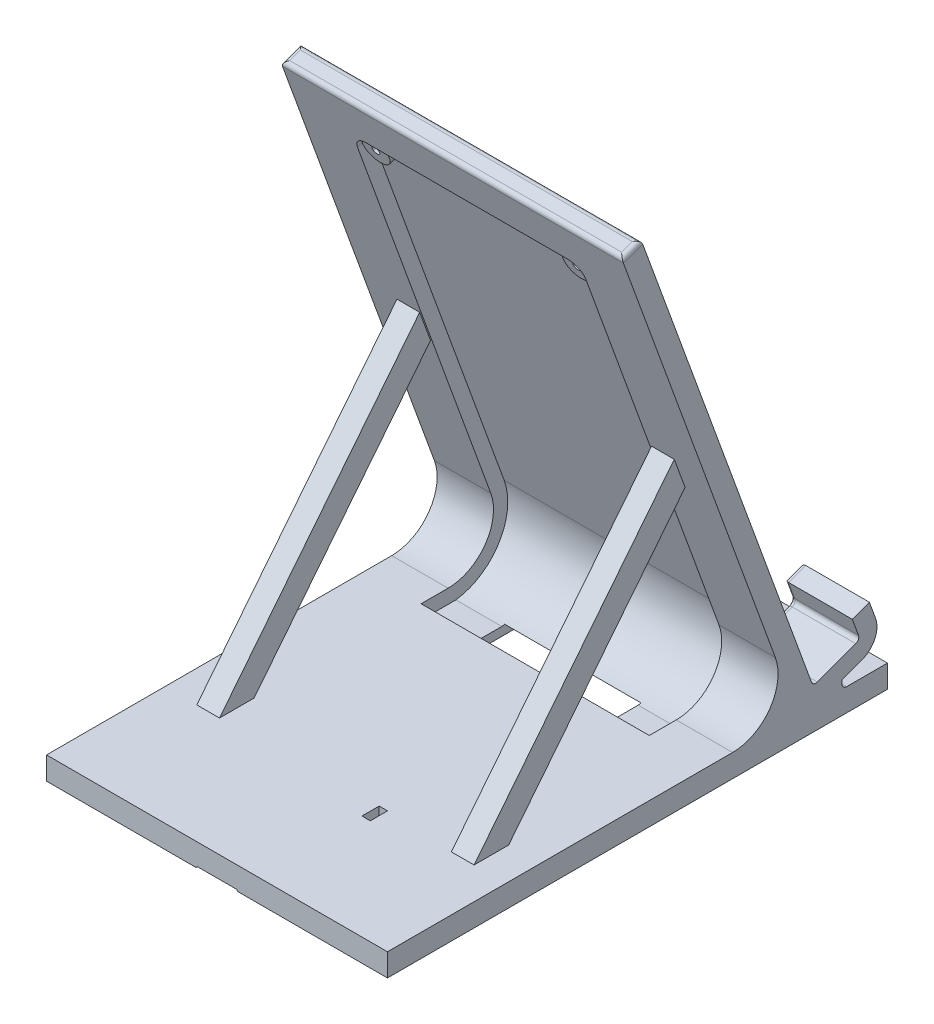
SolidWorks part; units mm, degrees
material "PLA"
ref_plane "前视基准面" through (0, 0, 0) normal (0, 0, 1) x (1, 0, 0)
ref_plane "上视基准面" through (0, 0, 0) normal (0, 1, 0) x (1, 0, 0)
ref_plane "右视基准面" through (0, 0, 0) normal (1, 0, 0) x (0, 0, -1)
other "Configuration Table"
sketch "草图1" plane through (0, 0, 0) normal (0, 1, 0) x (1, 0, 0)
  line L1 (-37.5, -55) -> (37.5, -55)
  line L2 (-37.5, -55) -> (-37.5, 55)
  line L3 (-37.5, 55) -> (37.5, 55)
  line L4 (37.5, -55) -> (37.5, 55)
  line L5 (-37.5, -55) -> (37.5, 55) construction
  line L6 (-37.5, 55) -> (37.5, -55) construction
  point P0 (0, 0)
  dimension "D1" = 75
  dimension "D2" = 110
extrude "底座凸台-拉伸1" add sketch "草图1" along normal blind 5
sketch "草图2" plane through (-37.5, 0, 0) normal (-1, 0, 0) x (0, 0, 1)
  line L0 (-35.2112, 5) -> (3.4371, 111.1853)
  line L1 (55, 5) -> (-55, 5) construction
  line L2 (3.4371, 111.1853) -> (-0.7915, 112.7244)
  line L3 (-0.7915, 112.7244) -> (-40, 5)
  line L4 (-55, 5) -> (-55, 0) construction
  line L5 (-40, 5) -> (-35.2112, 5)
  dimension "D1" = 4.5
  dimension "D2" = 70
  dimension "D3" = 15
  dimension "D4" = 113
extrude "支架面板凸台-拉伸2" add sketch "草图2" against normal up to surface (75 mm away) up to face at (37.5, 2.5, 0)
sketch "草图4" plane through (37.5, 0, 0) normal (1, 0, 0) x (0, 0, -1)
  line L0 (45, 6.8199) -> (49.3969, 8.4202)
  line L1 (52.3853, 14.8288) -> (51.0172, 18.5875)
  line L2 (51.0172, 18.5875) -> (47.2584, 17.2195)
  line L3 (47.2584, 17.2195) -> (48.6265, 13.4607)
  line L4 (38.6319, 8.7588) -> (48.0288, 12.179)
  line L5 (40, 5) -> (0.7915, 112.7244) construction
  line L6 (38.6319, 8.7588) -> (40, 5)
  line L9 (45, 5) -> (40, 5)
  line L10 (45, 6.8199) -> (45, 5)
  arc A0 (49.3969, 8.4202) -> (52.3853, 14.8288) centre (47.6868, 13.1187) ccw
  arc A1 (48.0288, 12.179) -> (48.6265, 13.4607) centre (47.6868, 13.1187) ccw
  dimension "D6" = 1
  dimension "D1" = 90
  dimension "D2" = 90
  dimension "D3" = 10
  dimension "D4" = 4
  dimension "D5" = 4
  dimension "D7" = 5
  dimension "D8" = 4
extrude "支点凸台-拉伸4" add sketch "草图4" against normal blind 15
mirror "镜向1" about plane through (0, 0, 0) normal (1, 0, 0) of "支点凸台-拉伸4"
fillet "圆角1" radius 10 1 edges at (0, 5, -35.2112)
sketch "草图5" plane through (-37.5, 0, 0) normal (-1, 0, 0) x (0, 0, 1)
  line L0 (-17.4763, 53.7262) -> (-15.091, 60.2798)
  line L1 (-30.3266, 18.4202) -> (3.4371, 111.1853) construction
  line L2 (-15.091, 60.2798) -> (28.9432, 5)
  line L3 (-20.9297, 5) -> (55, 5) construction
  line L4 (28.9432, 5) -> (21.3375, 5)
  line L5 (21.3375, 5) -> (-17.4763, 53.7262)
extrude "凸台-拉伸1" add sketch "草图5" along normal blind 5 from offset 12 offset against normal yes
mirror "镜向2" about plane through (0, 0, 0) normal (1, 0, 0) of "凸台-拉伸1"
sketch "草图7" plane through (0, 0, 0) normal (1, 0, 0) x (0, 0, -1)
  line L0 (2.8962, 102.8486) -> (-0.0169, 101.7883)
  line L2 (-3.4371, 111.1853) -> (30.3088, 18.4692) construction
  line L4 (-0.524, 112.2455) -> (33.2792, 19.3718) construction
  line L6 (15, 5) -> (20.7807, 5)
  line L7 (15, 1.9) -> (22.6528, 1.9)
  line L19 (-3.4371, 111.1853) -> (30.3266, 18.4202) construction
  line L20 (0.7915, 112.7244) -> (-3.4371, 111.1853) construction
  line L21 (30.3088, 18.4692) -> (20.9297, 15)
  line L22 (20.9297, 15) -> (20.7807, 5)
  line L23 (-55, 5) -> (-55, 0) construction
  line L33 (15, 5) -> (15, 1.9)
  line L45 (-0.0169, 101.7883) -> (30.3088, 18.4692)
  line L46 (2.8962, 102.8486) -> (33.2792, 19.3718)
  arc A6 (20.9297, 5) -> (30.3266, 18.4202) centre (20.9297, 15) ccw construction
  arc A19 (21.1077, 1.9173) -> (33.2792, 19.3718) centre (19.6222, 15.9242) ccw construction
  arc A20 (20.7807, 5) -> (30.3088, 18.4692) centre (19.6222, 15.9242) ccw construction
  arc A21 (33.2792, 19.3718) -> (22.6528, 1.9) centre (20.9693, 14.8914) cw
  dimension "D3" = 10
  dimension "D4" = 13.1
  dimension "D1" = 3.1
  dimension "D2" = 3.1
  dimension "D5" = 70
extrude "线圈槽位切除-拉伸2" cut sketch "草图7" against normal mid plane 50.2
sketch "草图8" plane through (0, 0, 0) normal (0, -1, 0) x (1, 0, 0)
  line L0 (0, 0) -> (0, -42.2617) construction
  line L1 (-5.9, 53.5) -> (5.9, 53.5)
  line L2 (-15, 39.7) -> (-15, -46.5)
  line L3 (-15, -46.5) -> (15, -46.5)
  line L4 (15, 39.7) -> (15, -46.5)
  line L5 (-5.8, 53.5) -> (-5.8, 39.7) construction
  line L6 (5.9, 53.5) -> (5.9, 39.7)
  line L7 (5.9, 39.7) -> (15, 39.7)
  line L8 (-5.9, 53.5) -> (-5.9, 39.7)
  line L9 (-5.9, 39.7) -> (-15, 39.7)
  line L10 (-37.5, 55) -> (37.5, 55) construction
  line L11 (-5.8, 39.7) -> (5.8, 39.7) construction
  line L12 (5.8, 39.7) -> (5.8, 53.5) construction
  dimension "D1" = 30
  dimension "D2" = 100
  dimension "D3" = 0.1
  dimension "D5" = 1.5
  dimension "D6" = 0.1
extrude "零件槽位切除-拉伸3" cut sketch "草图8" against normal blind 2
fillet "手机支点圆角2" radius 1 28 edges at (22.5, 15.3401, -47.9425) (22.5, 12.696, -48.5931) (22.5, 16.7082, -51.7012) (22.5, 11.0056, -52.2184) (22.5, 5.9099, -45) (22.5, 17.9035, -49.1378) (22.5, 10.4689, -43.3304) (22.5, 7.62, -47.1985) (-30, 8.7588, -38.6319) (-30, 5, -45) (30, 5, -45) (30, 8.7588, -38.6319) (0, 111.1853, 3.4371) (0, 112.7244, -0.7915) (37.5, 111.9548, 1.3228) (-37.5, 111.9548, 1.3228) (-22.5, 6.8794, -39.316) (-22.5, 10.4689, -43.3304) (-22.5, 12.696, -48.5931) (-22.5, 15.3401, -47.9425) (-22.5, 17.9035, -49.1378) (-22.5, 16.7082, -51.7012) (-22.5, 11.0056, -52.2184) (-22.5, 7.62, -47.1985) (-22.5, 5.9099, -45) (-22.5, 5, -42.5) (22.5, 6.8794, -39.316) (22.5, 5, -42.5)
sketch "草图9" plane through (0, 0, 55) normal (0, 0, 1) x (1, 0, 0)
  line L1 (-4.6, 0.3) -> (4.6, 0.3)
  line L2 (-4.6, 0.3) -> (-4.6, -0.8)
  line L3 (-4.6, -0.8) -> (4.6, -0.8)
  line L4 (4.6, 0.3) -> (4.6, -0.8)
  line L6 (4.5, -1.9) -> (4.5, -0.8) construction
  line L7 (-4.5, -1.9) -> (-4.5, -0.8) construction
  line L11 (-3.5, 0.2) -> (3.5, 0.2) construction
  dimension "D1" = 0.1
  dimension "D2" = 0.1
  dimension "D3" = 1
  dimension "D4" = 0.1
sketch "草图10" plane through (0, 0, 0) normal (0, 1, 0) x (1, 0, 0)
  circle A0 centre (-18, -34) radius 1
  circle A1 centre (18, -34) radius 1
  circle A2 centre (18, 34) radius 1
  circle A3 centre (-18, 34) radius 1
  dimension "D1" = 2
  dimension "D2" = 2
  dimension "D3" = 2
  dimension "D4" = 2
extrude "拉伸-薄壁1" add sketch "草图10" against normal up to surface (2 mm away) thin thin type one direction wall 2
sketch "草图11" plane through (0, 0, 0) normal (0, 1, 0) x (1, 0, 0)
  line L0 (-18, -28) -> (-18, 28)
  line L1 (18, -28) -> (18, 28)
  circle A0 centre (-18, -34) radius 6 construction
  circle A1 centre (-18, 34) radius 6 construction
  circle A2 centre (18, -34) radius 6 construction
  circle A3 centre (18, 34) radius 6 construction
extrude "拉伸-薄壁2" add sketch "草图11" against normal up to surface (2.4 mm away) thin thin type mid plane wall 1
extrude "切除-拉伸1" cut sketch "草图9" against normal up to surface (1.5 mm away)
sketch "草图12" plane through (0, 2, 0) normal (0, -1, 0) x (1, 0, 0)
  line L0 (7.9, 34.3906) -> (11.6, 34.3906)
  line L1 (8, 34.2906) -> (11.5, 34.2906) construction
  line L2 (8, 34.2906) -> (8, 25.7906) construction
  line L3 (8, 25.7906) -> (11.5, 25.7906) construction
  line L4 (11.5, 34.2906) -> (11.5, 25.7906) construction
  line L5 (11.6, 34.3906) -> (11.6, 25.6906)
  line L6 (7.9, 25.6906) -> (11.6, 25.6906)
  line L7 (7.9, 34.3906) -> (7.9, 25.6906)
  dimension "D1" = 0.1
extrude "开关拉伸-薄壁3" add sketch "草图12" along normal blind 3 thin thin type one direction wall 1.5
fillet "充电口圆角2" radius 0.5 2 edges at (-4.6, 0.3, 54.25) (4.6, 0.3, 54.25)
sketch "草图13" plane through (0, 2, 0) normal (0, -1, 0) x (1, 0, 0)
  line L0 (-8, 20.3812) -> (-8, 17.3812) construction
  line L1 (-8, 17.3812) -> (-10.5, 17.3812) construction
  line L2 (-10.5, 17.3812) -> (-10.5, -7.6188) construction
  line L3 (-10.5, -7.6188) -> (10.5, -7.6188) construction
  line L4 (10.5, -7.6188) -> (10.5, 17.3812) construction
  line L5 (10.5, 17.3812) -> (8, 17.3812) construction
  line L6 (8, 17.3812) -> (8, 20.3812) construction
  line L7 (8, 17.3812) -> (8, 20.3812) construction
  line L8 (8, 20.3812) -> (-8, 20.3812) construction
  line L9 (8, 20.3812) -> (-8, 20.3812) construction
  line L10 (10.5, 0.3812) -> (10.5, 17.3812) construction
  line L11 (-3.5, -7.6188) -> (3.5, -7.6188) construction
  line L12 (-8.1, 20.4812) -> (-8.1, 17.4812)
  line L13 (-8.1, 17.4812) -> (-10.6, 17.4812)
  line L14 (-10.6, 17.4812) -> (-10.6, -7.7188)
  line L15 (-10.6, -7.7188) -> (10.6, -7.7188)
  line L16 (10.6, -7.7188) -> (10.6, 17.4812)
  line L17 (10.6, 17.4812) -> (8.1, 17.4812)
  line L18 (8.1, 17.4812) -> (8.1, 20.4812)
  line L19 (8.1, 20.4812) -> (-8.1, 20.4812)
  dimension "D1" = 0.1
extrude "电路板固定拉伸-薄壁4" add sketch "草图13" along normal up to surface (2 mm away) thin up to face at (0.5, 0, 16.2417) thin type one direction wall 1.5
sketch "草图14" plane through (0, 2, 0) normal (0, -1, 0) x (1, 0, 0)
  line L0 (5.9, 39.7) -> (5.9, 39.6)
  line L1 (5.9, 39.6) -> (-5.9, 39.6)
  line L2 (-5.9, 39.6) -> (-5.9, 39.7)
  line L3 (-5.8, 39.7) -> (5.8, 39.7) construction
  line L4 (15, 39.7) -> (5.9, 39.7) construction
  line L7 (-5.9, 53.5) -> (-5.9, 39.7) construction
  line L8 (-5.9, 39.7) -> (-15, 39.7) construction
  line L17 (-5.9, 39.7) -> (-10.9, 39.7)
  line L21 (10.9, 39.7) -> (5.9, 39.7)
  dimension "D2" = 0.1
  dimension "D1" = 5
  dimension "D3" = 5
extrude "充电口拉伸-薄壁5" add sketch "草图14" along normal up to surface (2 mm away) thin up to face at (0.5, 0, 16.2417) thin type one direction reverse wall 2
sketch "草图15" plane through (0, 0, 0) normal (0, -1, 0) x (1, 0, 0)
  circle A0 centre (-18, 34) radius 1 construction
  circle A1 centre (-18, 34) radius 1
  circle A2 centre (18, 34) radius 1 construction
  circle A3 centre (18, 34) radius 1
  circle A4 centre (18, -34) radius 1 construction
  circle A5 centre (-18, -34) radius 1 construction
  circle A6 centre (18, -34) radius 1
  circle A7 centre (-18, -34) radius 1
extrude "螺丝孔切除-拉伸2" cut sketch "草图15" against normal blind 2
sketch "草图18" plane through (0, 5, 0) normal (0, 1, 0) x (1, 0, 0)
  line L0 (0, 55) -> (0, 40) construction
  line L1 (37.5, 55) -> (-37.5, 55) construction
  line L2 (21.5, 40) -> (-21.5, 40) construction
  line L3 (12.8007, 50) -> (-12.8007, 50) construction
  text T0 "Alice Feng"
  dimension "D1" = 5
extrude "切除-拉伸2" cut sketch "草图18" against normal blind 0.25
sketch "草图19" plane through (0, 12.9618, -35.6123) normal (0, -0.342, 0.9397) x (1, 0, 0)
  line L0 (0, 95.6555) -> (0, 75.4237) construction
  line L1 (-25.1, 95.6555) -> (25.1, 95.6555) construction
  line L2 (-25.1, 95.6555) -> (-25.1, 6.937) construction
  line L7 (25.1, 95.6555) -> (25.1, 92.6555)
  line L8 (22.1, 95.6555) -> (25.1, 95.6555)
  line L9 (-25.1, 92.6555) -> (-25.1, 95.6555)
  line L11 (-25.1, 95.6555) -> (-22.1, 95.6555)
  arc A2 (-25.1, 92.6555) -> (-22.1, 95.6555) centre (-22.1, 92.6555) ccw
  circle A3 centre (-22.1, 92.6555) radius 0.825
  circle A4 centre (22.1, 92.6555) radius 0.825
  arc A5 (25.1, 92.6555) -> (22.1, 95.6555) centre (22.1, 92.6555) cw
  dimension "D3" = 1.65
  dimension "D1" = 3
  dimension "D2" = 3
extrude "凸台-拉伸2" add sketch "草图19" along normal blind 2
sketch "草图20" plane through (0, 12.2778, -33.7329) normal (0, -0.342, 0.9397) x (1, 0, 0)
  line L0 (-25.1, 92.6555) -> (-25.1, 95.6555)
  line L1 (-25.1, 95.6555) -> (-22.1, 95.6555)
  line L2 (0, 95.6555) -> (0, 71.8622) construction
  line L3 (-25.1, 95.6555) -> (25.1, 95.6555) construction
  line L5 (25.1, 95.6555) -> (22.1, 95.6555)
  line L12 (25.1, 92.6555) -> (25.1, 95.6555)
  arc A0 (-25.1, 92.6555) -> (-22.1, 95.6555) centre (-22.1, 92.6555) ccw construction
  arc A6 (-22.1, 95.6555) -> (-25.1, 92.6555) centre (-22.1, 92.6555) ccw
  arc A7 (22.1, 95.6555) -> (25.1, 92.6555) centre (22.1, 92.6555) cw
extrude "凸台-拉伸3" add sketch "草图20" along normal blind 1.1
sketch "草图22" plane through (0, 0, 0) normal (0, 0, 1) x (1, 0, 0)
  line L0 (0, 0) -> (0, 9.0871) construction
  line L1 (-25.1, 3.3) -> (-5.4, 3.3)
  line L2 (-25.1, 3.3) -> (-25.1, 1.9)
  line L3 (-25.1, 1.9) -> (-5.4, 1.9)
  line L4 (-5.4, 3.3) -> (-5.4, 1.9)
  line L5 (-5.5, 3.2) -> (-25, 3.2) construction
  line L6 (-5.5, 2) -> (-5.5, 19.4463) construction
  line L7 (-15, 2) -> (15, 2) construction
  line L8 (-25, 19.4463) -> (-25, 2) construction
  line L9 (5.4, 3.3) -> (5.4, 1.9)
  line L10 (25.1, 1.9) -> (5.4, 1.9)
  line L11 (25.1, 3.3) -> (25.1, 1.9)
  line L12 (25.1, 3.3) -> (5.4, 3.3)
  dimension "D1" = 0.1
  dimension "D2" = 0.1
  dimension "D3" = 0.1
  dimension "D4" = 0.1
extrude "切除-拉伸3" cut sketch "草图22" along normal blind 2.1 from surface starting at face at (0, 2.7, -15)
chamfer "倒角1" distance 1 angle 45 1 edges at (0, 2, -15)
sketch "草图23" plane through (0, 13.4406, -36.9279) normal (0, 0.342, -0.9397) x (-1, 0, 0)
  line L0 (22.1, 95.6555) -> (-22.1, 95.6555) construction
  line L1 (22.1, 95.6555) -> (-22.1, 95.6555) construction
  line L2 (22.1, 96.6555) -> (-22.1, 96.6555) construction
  text T1 "Alice Feng"
  dimension "D1" = 1
extrude "切除-拉伸4" cut sketch "草图23" against normal blind 0.2
sketch "草图24" plane through (0, 5, 0) normal (0, 1, 0) x (1, 0, 0)
  line L0 (10.57, -28.2406) -> (8.93, -28.2406) construction
  line L1 (10.57, -28.2406) -> (8.93, -28.2406) construction
  line L2 (10.57, -30.0406) -> (10.57, -28.2406) construction
  line L3 (10.57, -30.0406) -> (10.57, -28.2406) construction
  line L4 (10.57, -31.8406) -> (10.57, -30.0406) construction
  line L5 (10.57, -31.8406) -> (10.57, -30.0406) construction
  line L6 (8.93, -31.8406) -> (10.57, -31.8406) construction
  line L7 (8.93, -31.8406) -> (10.57, -31.8406) construction
  line L24 (8.93, -28.2406) -> (8.93, -30.0406) construction
  line L25 (8.93, -28.2406) -> (8.93, -30.0406) construction
  line L26 (8.93, -30.0406) -> (8.93, -31.8406) construction
  line L27 (8.93, -30.0406) -> (8.93, -31.8406) construction
  line L28 (10.67, -28.1406) -> (8.83, -28.1406)
  line L29 (8.83, -28.1406) -> (8.83, -30.0406)
  line L30 (8.83, -30.0406) -> (8.83, -31.9406)
  line L31 (8.83, -31.9406) -> (10.67, -31.9406)
  line L32 (10.67, -31.9406) -> (10.67, -30.0406)
  line L33 (10.67, -30.0406) -> (10.67, -28.1406)
  dimension "D1" = 0.1
extrude "切除-拉伸5" cut sketch "草图24" against normal up to next
